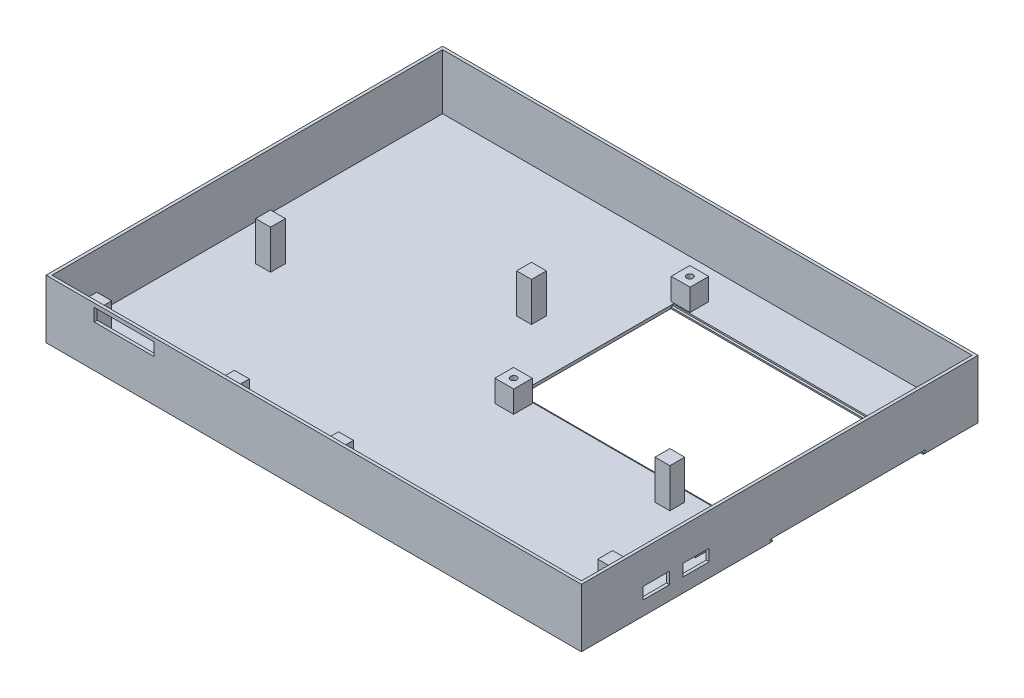
SolidWorks part; units mm, degrees
material "PLA"
ref_plane "Спереди" through (0, 0, 0) normal (0, 0, 1) x (1, 0, 0)
ref_plane "Сверху" through (0, 0, 0) normal (0, 1, 0) x (1, 0, 0)
ref_plane "Справа" through (0, 0, 0) normal (1, 0, 0) x (0, 0, -1)
sketch "Эскиз1" plane through (0, 0, 0) normal (0, 1, 0) x (1, 0, 0)
  line L1 (135, 100) -> (-135, 100)
  line L2 (135, 100) -> (135, -100)
  line L3 (135, -100) -> (-135, -100)
  line L4 (-135, 100) -> (-135, -100)
  line L5 (135, 100) -> (-135, -100) construction
  line L6 (135, -100) -> (-135, 100) construction
  point P0 (0, 0)
  dimension "D1" = 200
  dimension "D2" = 270
extrude "Бобышка-Вытянуть1" add sketch "Эскиз1" along normal blind 1.5
sketch "Эскиз2" plane through (0, 1.5, 0) normal (0, 1, 0) x (1, 0, 0)
  line L0 (133.5, 98.5) -> (-133.5, 98.5)
  line L1 (-133.5, 98.5) -> (-133.5, -98.5)
  line L2 (-133.5, -98.5) -> (-110.7, -98.5)
  line L3 (133.5, -98.5) -> (133.5, 98.5)
  line L4 (-135, 100) -> (-135, -100)
  line L5 (-135, -100) -> (135, -100)
  line L6 (135, -100) -> (135, 100)
  line L7 (135, 100) -> (-135, 100)
  line L8 (-135, 100) -> (-135, -100)
  line L9 (-135, -100) -> (-110.7, -100)
  line L10 (135, -100) -> (135, 100)
  line L11 (135, 100) -> (-135, 100)
  line L12 (-110.7, -98.5) -> (-110.7, -100)
  line L14 (-80.5, -98.5) -> (-80.5, -100)
  line L16 (-80.5, -98.5) -> (133.5, -98.5)
  line L17 (-80.5, -100) -> (135, -100)
  line L18 (-133.5, -98.5) -> (133.5, -98.5) construction
  line L20 (-135, -100) -> (135, -100) construction
  dimension "D3" = 24.3
  dimension "D4" = 54.5
  dimension "D1" = 0
  dimension "D2" = 1.5
extrude "Бобышка-Вытянуть2" add sketch "Эскиз2" along normal offset from surface (28 mm away) 7 offset beyond the face yes
sketch "Эскиз3" plane through (0, 1.5, 0) normal (0, 1, 0) x (1, 0, 0)
  line L1 (-110.7, -98.5) -> (-80.5, -98.5)
  line L2 (-110.7, -98.5) -> (-110.7, -100)
  line L3 (-110.7, -100) -> (-80.5, -100)
  line L4 (-80.5, -98.5) -> (-80.5, -100)
extrude "Бобышка-Вытянуть3" add sketch "Эскиз3" along normal blind 19.7
sketch "Эскиз4" plane through (-110.7, 0, 0) normal (1, 0, 0) x (0, 0, -1)
  line L0 (-100, 29.5) -> (-100, 21.2) construction
  line L1 (-98.5, 29.5) -> (-100, 29.5)
  line L2 (-98.5, 29.5) -> (-98.5, 27.6)
  line L3 (-98.5, 27.6) -> (-100, 27.6)
  line L4 (-100, 29.5) -> (-100, 27.6)
  dimension "D1" = 1.9
extrude "Бобышка-Вытянуть4" add sketch "Эскиз4" along normal up to surface (30.2 mm away) up to face at (-80.5, 25.35, 99.25)
sketch "Эскиз5" plane through (135, 0, 0) normal (1, 0, 0) x (0, 0, -1)
  line L0 (-100, 29.5) -> (-100, 0) construction
  line L1 (-55.55, 13) -> (-68.85, 13)
  line L2 (-55.55, 13) -> (-55.55, 7.1)
  line L3 (-55.55, 7.1) -> (-68.85, 7.1)
  line L4 (-68.85, 13) -> (-68.85, 7.1)
  line L5 (-55.55, 13) -> (-68.85, 7.1) construction
  line L6 (-55.55, 7.1) -> (-68.85, 13) construction
  line L7 (-35.55, 13) -> (-48.85, 13)
  line L8 (-35.55, 13) -> (-35.55, 7.1)
  line L9 (-35.55, 7.1) -> (-48.85, 7.1)
  line L10 (-48.85, 13) -> (-48.85, 7.1)
  line L11 (-35.55, 13) -> (-48.85, 7.1) construction
  line L12 (-35.55, 7.1) -> (-48.85, 13) construction
  line L13 (-100, 0) -> (100, 0) construction
  point P0 (-62.2, 10.05)
  point P5 (-42.2, 10.05)
  dimension "D1" = 13.3
  dimension "D2" = 5.9
  dimension "D3" = 6.7
  dimension "D4" = 31.15
  dimension "D5" = 13
extrude "Вырез-Вытянуть1" cut sketch "Эскиз5" against normal up to surface (1.5 mm away) up to face at (133.5, 15.5, 0)
sketch "Эскиз6" plane through (0, 1.5, 0) normal (0, 1, 0) x (1, 0, 0)
  line L0 (-133.5, 98.5) -> (133.5, 98.5) construction
  line L5 (6.2, 74.1) -> (15.7, 74.1)
  line L6 (6.2, 74.1) -> (6.2, 83.5)
  line L7 (6.2, 83.5) -> (15.7, 83.5)
  line L8 (15.7, 74.1) -> (15.7, 83.5)
  line L9 (133.5, 98.5) -> (133.5, -98.5) construction
  line L11 (133.5, -98.5) -> (-133.5, -98.5) construction
  line L12 (133.5, 74.1) -> (124, 74.1)
  line L13 (133.5, 74.1) -> (133.5, 83.5)
  line L14 (133.5, 83.5) -> (124, 83.5)
  line L15 (124, 74.1) -> (124, 83.5)
  line L16 (6.2, -5.45) -> (15.7, -5.45)
  line L17 (6.2, -5.45) -> (6.2, -14.85)
  line L18 (6.2, -14.85) -> (15.7, -14.85)
  line L19 (15.7, -5.45) -> (15.7, -14.85)
  line L21 (124, -5.45) -> (133.5, -5.45)
  line L22 (124, -5.45) -> (124, -14.85)
  line L23 (124, -14.85) -> (133.5, -14.85)
  line L24 (133.5, -5.45) -> (133.5, -14.85)
  dimension "D1" = 24.4
  dimension "D2" = 127.3
  dimension "D3" = 9.4
  dimension "D4" = 9.5
  dimension "D5" = 93.05
extrude "Бобышка-Вытянуть5" add sketch "Эскиз6" along normal blind 11.05
sketch "Эскиз7" plane through (0, 12.55, 0) normal (0, 1, 0) x (1, 0, 0)
  line L0 (15.7, 83.5) -> (6.2, 74) construction
  line L1 (6.2, 74) -> (15.7, 74) construction
  line L2 (15.7, 74) -> (6.2, 83.5) construction
  line L3 (15.7, -5.35) -> (6.2, -14.85) construction
  line L4 (15.7, -14.85) -> (6.2, -5.35) construction
  line L5 (133.5, 74) -> (124, 83.5) construction
  line L6 (133.5, 83.5) -> (124, 74) construction
  line L7 (133.5, -5.35) -> (124, -14.85) construction
  line L8 (133.5, -14.85) -> (124, -5.35) construction
  line L9 (6.2, -5.35) -> (15.7, -5.35) construction
  line L10 (133.5, 74.1) -> (133.5, -5.45) construction
  line L11 (133.5, -5.35) -> (124, -5.35) construction
  line L12 (124, 74) -> (133.5, 74) construction
  circle A0 centre (128.75, -10.1) radius 1.6
  circle A1 centre (128.75, 78.75) radius 1.6
  circle A2 centre (10.95, 78.75) radius 1.6
  circle A3 centre (10.95, -10.1) radius 1.6
  dimension "D1" = 3.2
  dimension "D2" = 0.1
  dimension "D3" = 0.1
extrude "Вырез-Вытянуть2" cut sketch "Эскиз7" against normal blind 6
sketch "Эскиз8" plane through (0, 1.5, 0) normal (0, 1, 0) x (1, 0, 0)
  line L0 (133.5, -5.45) -> (124, -5.45) construction
  line L1 (135, 72.4) -> (7.7, 72.4)
  line L2 (135, 72.4) -> (135, -3.75)
  line L3 (135, -3.75) -> (7.7, -3.75)
  line L4 (7.7, 72.4) -> (7.7, -3.75)
  line L5 (124, 74.1) -> (133.5, 74.1) construction
  line L7 (6.2, 83.5) -> (6.2, 74.1) construction
  line L8 (135, -100) -> (135, 100) construction
  dimension "D1" = 1.7
  dimension "D2" = 1.7
  dimension "D3" = 1.5
extrude "Вырез-Вытянуть3" cut sketch "Эскиз8" against normal through all
sketch "Эскиз9" plane through (135, 0, 0) normal (1, 0, 0) x (0, 0, -1)
  line L0 (34.325, 1.5) -> (34.325, 50001.5) construction
  line L1 (-3.75, 1.5) -> (-4.95, 1.5)
  line L2 (-3.75, 1.5) -> (-3.75, 0.7)
  line L3 (-3.75, 0.7) -> (-4.95, 0.7)
  line L4 (-4.95, 1.5) -> (-4.95, 0.7)
  line L9 (72.4, 1.5) -> (-3.75, 1.5) construction
  line L10 (72.4, 0.7) -> (73.6, 0.7)
  line L11 (73.6, 1.5) -> (73.6, 0.7)
  line L12 (72.4, 1.5) -> (73.6, 1.5)
  line L13 (72.4, 1.5) -> (72.4, 0.7)
  point P14 (34.325, 1.5)
  dimension "D1" = 0.8
  dimension "D2" = 1.2
extrude "Вырез-Вытянуть4" cut sketch "Эскиз9" against normal up to surface (127.3 mm away) up to face at (7.7, 0.75, -34.325)
sketch "Эскиз10" plane through (0, 1.5, 0) normal (0, 1, 0) x (1, 0, 0)
  line L0 (133.5, -14.85) -> (133.5, -98.5) construction
  line L1 (124.175, -24.225) -> (116.675, -24.225)
  line L2 (124.175, -24.225) -> (124.175, -31.725)
  line L3 (124.175, -31.725) -> (116.675, -31.725)
  line L4 (116.675, -24.225) -> (116.675, -31.725)
  line L5 (124.175, -24.225) -> (116.675, -31.725) construction
  line L6 (124.175, -31.725) -> (116.675, -24.225) construction
  line L7 (114.55, -56.3) -> (107.05, -56.3)
  line L8 (114.55, -56.3) -> (114.55, -63.8)
  line L9 (114.55, -63.8) -> (107.05, -63.8)
  line L10 (107.05, -56.3) -> (107.05, -63.8)
  line L11 (114.55, -56.3) -> (107.05, -63.8) construction
  line L12 (114.55, -63.8) -> (107.05, -56.3) construction
  line L13 (115.175, -89.275) -> (107.675, -89.275)
  line L14 (115.175, -89.275) -> (115.175, -96.775)
  line L15 (115.175, -96.775) -> (107.675, -96.775)
  line L16 (107.675, -89.275) -> (107.675, -96.775)
  line L17 (115.175, -89.275) -> (107.675, -96.775) construction
  line L18 (115.175, -96.775) -> (107.675, -89.275) construction
  line L19 (133.5, -98.5) -> (-133.5, -98.5) construction
  point P0 (120.425, -27.975)
  point P5 (110.8, -60.05)
  point P10 (111.425, -93.025)
  dimension "D1" = 13.075
  dimension "D2" = 70.525
  dimension "D3" = 22.7
  dimension "D4" = 38.45
  dimension "D5" = 22.075
  dimension "D6" = 5.475
  dimension "D7" = 7.5
extrude "Бобышка-Вытянуть6" add sketch "Эскиз10" along normal blind 6.9
sketch "Эскиз11" plane through (0, 1.5, 0) normal (0, 1, 0) x (1, 0, 0)
  line L1 (-46.7446, -85.75) -> (-54.2446, -85.75)
  line L2 (-46.7446, -85.75) -> (-46.7446, -93.25)
  line L3 (-46.7446, -93.25) -> (-54.2446, -93.25)
  line L4 (-54.2446, -85.75) -> (-54.2446, -93.25)
  line L5 (-46.7446, -85.75) -> (-54.2446, -93.25) construction
  line L6 (-46.7446, -93.25) -> (-54.2446, -85.75) construction
  line L7 (-19.0224, 28.8491) -> (-26.5224, 28.8491)
  line L8 (-19.0224, 28.8491) -> (-19.0224, 36.3491)
  line L9 (-19.0224, 36.3491) -> (-26.5224, 36.3491)
  line L10 (-26.5224, 28.8491) -> (-26.5224, 36.3491)
  line L11 (-19.0224, 28.8491) -> (-26.5224, 36.3491) construction
  line L12 (-19.0224, 36.3491) -> (-26.5224, 28.8491) construction
  line L13 (-115.5446, -93.8424) -> (-123.0446, -93.8424)
  line L14 (-115.5446, -93.8424) -> (-115.5446, -86.3424)
  line L15 (-115.5446, -86.3424) -> (-123.0446, -86.3424)
  line L16 (-123.0446, -93.8424) -> (-123.0446, -86.3424)
  line L17 (-115.5446, -93.8424) -> (-123.0446, -86.3424) construction
  line L18 (-115.5446, -86.3424) -> (-123.0446, -93.8424) construction
  line L19 (-107.65, -14.1324) -> (-115.15, -14.1324)
  line L20 (-107.65, -14.1324) -> (-107.65, -6.6324)
  line L21 (-107.65, -6.6324) -> (-115.15, -6.6324)
  line L22 (-115.15, -14.1324) -> (-115.15, -6.6324)
  line L23 (-107.65, -14.1324) -> (-115.15, -6.6324) construction
  line L24 (-107.65, -6.6324) -> (-115.15, -14.1324) construction
  line L25 (97.2279, -17.6196) -> (89.7279, -17.6196)
  line L26 (97.2279, -17.6196) -> (97.2279, -10.1196)
  line L27 (97.2279, -10.1196) -> (89.7279, -10.1196)
  line L28 (89.7279, -17.6196) -> (89.7279, -10.1196)
  line L29 (97.2279, -17.6196) -> (89.7279, -10.1196) construction
  line L30 (97.2279, -10.1196) -> (89.7279, -17.6196) construction
  line L31 (94.0554, -99.0196) -> (86.5554, -99.0196)
  line L32 (94.0554, -99.0196) -> (94.0554, -91.5196)
  line L33 (94.0554, -91.5196) -> (86.5554, -91.5196)
  line L34 (86.5554, -99.0196) -> (86.5554, -91.5196)
  line L35 (94.0554, -99.0196) -> (86.5554, -91.5196) construction
  line L36 (94.0554, -91.5196) -> (86.5554, -99.0196) construction
  line L37 (6.3554, -93.8285) -> (-1.1446, -93.8285)
  line L38 (6.3554, -93.8285) -> (6.3554, -86.3285)
  line L39 (6.3554, -86.3285) -> (-1.1446, -86.3285)
  line L40 (-1.1446, -93.8285) -> (-1.1446, -86.3285)
  line L41 (6.3554, -93.8285) -> (-1.1446, -86.3285) construction
  line L42 (6.3554, -86.3285) -> (-1.1446, -93.8285) construction
  line L44 (-133.5, 98.5) -> (133.5, 98.5) construction
  line L45 (-133.5, -98.5) -> (-133.5, 98.5) construction
  line L47 (133.5, -98.5) -> (-133.5, -98.5) construction
  line L48 (133.5, -14.85) -> (133.5, -98.5) construction
  point P0 (-50.4946, -89.5)
  point P5 (-22.7724, 32.5991)
  point P10 (-119.2946, -90.0924)
  point P15 (-111.4, -10.3824)
  point P20 (93.4779, -13.8696)
  point P25 (90.3054, -95.2696)
  point P30 (2.6054, -90.0785)
  point P35 (-22.4719, 69.0881)
  point P36 (-12.0157, 72.8381)
  point P37 (-16.1848, 86.9618)
  point P38 (-4.1542, 61.9263)
  point P43 (-117.4296, -95.8215)
  point P45 (-67.739, -98.5)
  point P46 (-116.3398, -98.5)
  point P47 (0, 0)
  point P51 (0, 0)
  dimension "D1" = 7.5
  dimension "D2" = 65.9009
  dimension "D3" = 110.7276
  dimension "D4" = 108.8824
  dimension "D5" = 22.1
  dimension "D6" = 8.4076
  dimension "D7" = 14.2054
  dimension "D8" = 8.4215
  dimension "D9" = 130.8946
  dimension "D10" = 9
  dimension "D11" = 83.0054
  dimension "D12" = 3.2304
  dimension "D13" = 43.1946
  dimension "D14" = 84.6304
  dimension "D15" = 40.0221
extrude "Бобышка-Вытянуть7" add sketch "Эскиз11" along normal blind 19.7
